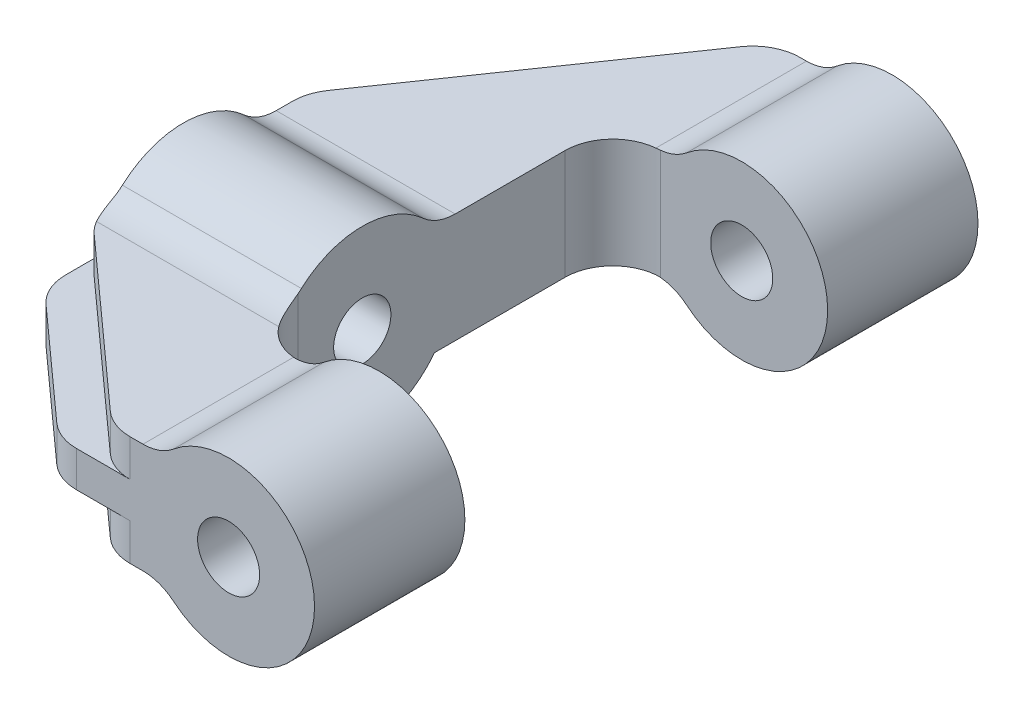
SolidWorks part; units mm, degrees
ref_plane "Front Plane" through (0, 0, 0) normal (0, 0, 1) x (1, 0, 0)
ref_plane "Top Plane" through (0, 0, 0) normal (0, 1, 0) x (1, 0, 0)
ref_plane "Right Plane" through (0, 0, 0) normal (1, 0, 0) x (0, 0, -1)
sketch "Sketch1" plane through (0, 0, 0) normal (0, 1, 0) x (1, 0, 0)
  line L0 (0, -15.0349) -> (0, 18.2065) construction
  line L1 (1.3, 16.8) -> (3.6, 16.8)
  line L2 (3.6, 16.8) -> (3.6, 10.5)
  line L3 (3.6, 10.5) -> (1.3, 10.5)
  line L4 (1.3, 10.5) -> (1.3, 16.8)
  line L5 (1.3, -4.7) -> (1.3, -11)
  line L6 (1.3, -11) -> (3.6, -11)
  line L7 (3.6, -11) -> (3.6, -4.7)
  line L8 (3.6, -4.7) -> (1.3, -4.7)
  dimension "D1" = 27.8
  dimension "D2" = 6.3
  dimension "D3" = 6.3
  dimension "D4" = 7.2
  dimension "D5" = 2.6
  dimension "D6" = 11
revolve "Revolve1" add sketch "Sketch1" angle 360 about L0
sketch "Sketch3" plane through (0, 0, 0) normal (0, 1, 0) x (1, 0, 0)
  line L0 (0, 0) -> (-19.765, 0) construction
  line L1 (-12.9, 3.8) -> (-12.9, 1.2)
  line L2 (-12.9, 1.2) -> (-5.4, 1.2)
  line L3 (-5.4, 1.2) -> (-5.4, 3.8)
  line L4 (-5.4, 3.8) -> (-12.9, 3.8)
  line L5 (3.6, -11) -> (3.6, -4.7) construction
  dimension "D1" = 7.6
  dimension "D2" = 2.4
  dimension "D3" = 7.5
  dimension "D4" = 9
revolve "Revolve2" add sketch "Sketch3" angle 360 about L0
sketch "Sketch4" plane through (0, 0, 0) normal (0, 1, 0) x (1, 0, 0)
  line L0 (-1.3, -4.7) -> (-5.4, -4.7)
  line L1 (-5.4, -4.7) -> (-5.4, -1.2)
  line L2 (-5.4, -1.2) -> (-12.9, -1.2)
  line L3 (-12.9, -1.2) -> (-12.9, -3.8)
  line L4 (-12.9, -3.8) -> (-5.4, -3.8) construction
  line L5 (-12.9, -3.8) -> (-4.9, -11)
  line L6 (-4.9, -11) -> (-1.3, -11)
  line L7 (-1.3, -11) -> (-1.3, -4.7)
  line L8 (-5.4, 1.2) -> (-5.4, 10.5)
  line L9 (-5.4, 10.5) -> (-1.3, 10.5)
  line L10 (-1.3, 10.5) -> (-1.3, 16.8)
  line L11 (-1.3, 16.8) -> (-4.9, 16.8)
  line L12 (-4.9, 16.8) -> (-12.9, 5.2)
  line L13 (-12.9, 5.2) -> (-12.9, 1.2)
  line L14 (-12.9, 1.2) -> (-5.4, 1.2)
  line L15 (-1.3, -11) -> (1.3, -11) construction
  line L16 (1.3, -4.7) -> (-1.3, -4.7) construction
  line L17 (-12.9, 1.2) -> (-12.9, -1.2) construction
  dimension "D1" = 4
  dimension "D2" = 3.6
extrude "Boss-Extrude1" add sketch "Sketch4" along normal blind 2.3 and the other way blind 2.3
sketch "Sketch5" plane through (0, 0, 0) normal (0, 1, 0) x (1, 0, 0)
  line L0 (-12.9, 5.2) -> (-12.9, 7.8421)
  line L1 (-12.9, 7.8421) -> (-6.7221, 16.8)
  line L2 (-6.7221, 16.8) -> (-4.9, 16.8)
  line L3 (-4.9, -11) -> (-7.1423, -11)
  line L4 (-7.1423, -11) -> (-12.9, -5.818)
  line L5 (-12.9, -5.818) -> (-12.9, -3.8)
  line L6 (-12.9, -3.8) -> (-4.9, -11)
  line L7 (-4.9, 16.8) -> (-12.9, 5.2)
  dimension "D1" = 1.5
  dimension "D2" = 1.5
extrude "Boss-Extrude2" add sketch "Sketch5" along normal blind 0.75 and the other way blind 0.75
fillet "Fillet1" radius 2 14 edges at (-7.1423, 0, 11) (-12.9, 0, 5.818) (-6.7221, 0, -16.8) (-12.9, 0, -7.8421) (-12.9, 1.525, -5.2) (-12.9, -1.525, -5.2) (-12.9, -1.525, 3.8) (-12.9, 1.525, 3.8) (-4.9, -1.525, 11) (-4.9, 1.525, 11) (-4.9, -1.525, -16.8) (-4.9, 1.525, -16.8) (-5.4, 0, 4.7) (-5.4, 0, -10.5)
fillet "Fillet2" radius 2 6 edges at (-2.7695, -2.3, 7.85) (-2.7695, -2.3, -13.65) (-9.15, 2.3, -3.0249) (-9.135, 2.3, 3.0249) (-2.7695, 2.3, -13.65) (-2.7695, 2.3, 7.85)
